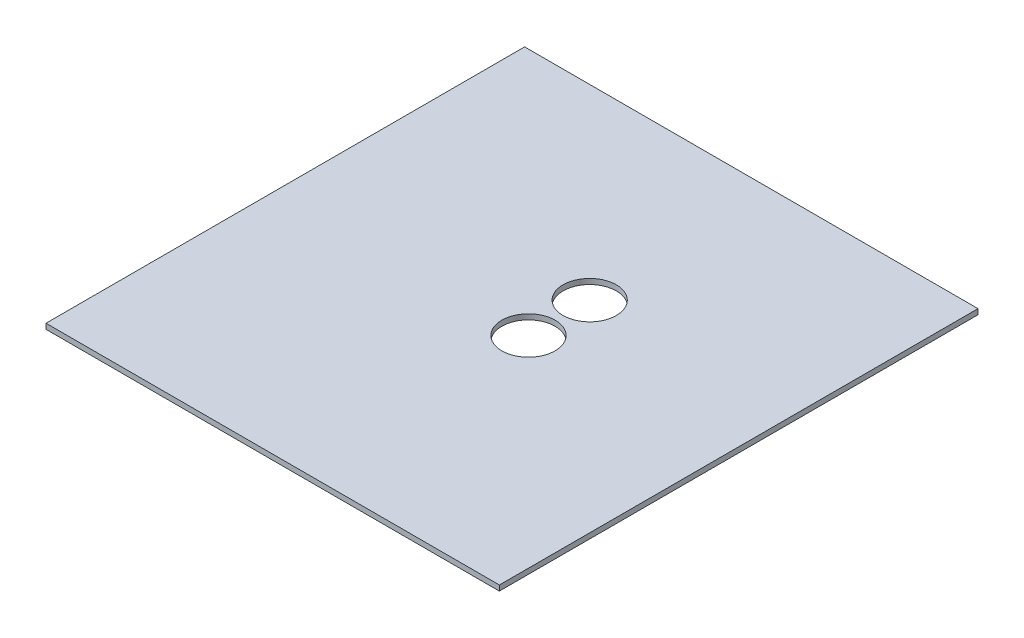
SolidWorks part; units mm, degrees
ref_plane "Front Plane" through (0, 0, 0) normal (0, 0, 1) x (1, 0, 0)
ref_plane "Top Plane" through (0, 0, 0) normal (0, 1, 0) x (1, 0, 0)
ref_plane "Right Plane" through (0, 0, 0) normal (1, 0, 0) x (0, 0, -1)
sketch "Sketch1" plane through (0, 0, 0) normal (0, 1, 0) x (1, 0, 0)
  line L1 (-44.6263, 26.2719) -> (125.6851, 26.2719)
  line L2 (-44.6263, 26.2719) -> (-44.6263, -153.5293)
  line L3 (-44.6263, -153.5293) -> (125.6851, -153.5293)
  line L4 (125.6851, 26.2719) -> (125.6851, -153.5293)
base flange "Base-Flange1" sketch "Sketch1" thickness 2 reverse thickness direction no parameters "D1"=0.7366
sketch "Sketch2" plane through (0, 0, 0) normal (0, 1, 0) x (1, 0, 0)
  circle A0 centre (49.9865, -43.8958) radius 10
  circle A1 centre (49.9865, -66.8958) radius 10
  dimension "D1" = 23
extrude "Cut-Extrude1" cut sketch "Sketch2" against normal blind 10
sketch "Bend-Lines1" [suppressed] plane through (0, 0, 0) normal (0, 1, 0) x (1, 0, 0)
sketch "Bounding-Box1" [suppressed] plane through (0, 0, 0) normal (0, 1, 0) x (1, 0, 0)
sheet metal parameters "Sheet-Metal1" thickness 2 parameters "D1"=0.7366
flat pattern "Flat-Pattern1" [suppressed]
sketch "Bend-Lines2" plane through (0, 0, 0) normal (0, 1, 0) x (1, 0, 0)
sketch3d "Bounding-Box2" [suppressed]
  line L0 (-44.6263, 26.2719, 0) -> (-44.6263, -153.5293, 0) construction
  line L1 (125.6851, 26.2719, 0) -> (125.6851, -153.5293, 0) construction
  line L2 (-44.6263, 26.2719, 0) -> (125.6851, 26.2719, 0) construction
  line L3 (-44.6263, -153.5293, 0) -> (125.6851, -153.5293, 0) construction
sketch "Sketch157-2" [suppressed] plane through (0, 0, 0) normal (0, 1, 0) x (1, 0, 0)
  line L0 (-44.6263, 26.2719) -> (125.6851, -153.5293) construction
  line L1 (-44.6263, -153.5293) -> (125.6851, 26.2719) construction
sketch "Sketch157-3" [suppressed] plane through (0, 0, 0) normal (0, 1, 0) x (1, 0, 0)
  line L0 (-44.6263, 26.2719) -> (65.7398, -39.4679) construction
  line L1 (-44.6263, -39.4679) -> (65.7398, 26.2719) construction
sketch "Sketch161-1" plane through (41.1691, 0, 63.5314) normal (0, 1, 0) x (0, 0, -1)
  line L5 (11.4891, -40) -> (11.4891, 40)
  line L6 (-11.4891, 40) -> (-11.4891, -40)
  line L7 (0, 0) -> (26.3777, 0) construction
  line L8 (0, 0) -> (0, 52.7554) construction
  line L9 (0, 3.4502) -> (0, 0)
  arc A2 (11.4891, 40) -> (-11.4891, 40) centre (0, 40) ccw
  arc A3 (-11.4891, -40) -> (11.4891, -40) centre (0, -40) ccw
sheet metal parameters "Sheet-Metal24" thickness 2 parameters "D1"=0.7366
flat pattern "Flat-Pattern1"
sketch "Bend-Lines2" plane through (0, 0, 0) normal (0, 1, 0) x (1, 0, 0)
sketch3d "Bounding-Box2" [suppressed]
  line L0 (-44.6263, 26.2719, 0) -> (-44.6263, -153.5293, 0) construction
  line L1 (125.6851, 26.2719, 0) -> (125.6851, -153.5293, 0) construction
  line L2 (-44.6263, 26.2719, 0) -> (125.6851, 26.2719, 0) construction
  line L3 (-44.6263, -153.5293, 0) -> (125.6851, -153.5293, 0) construction
